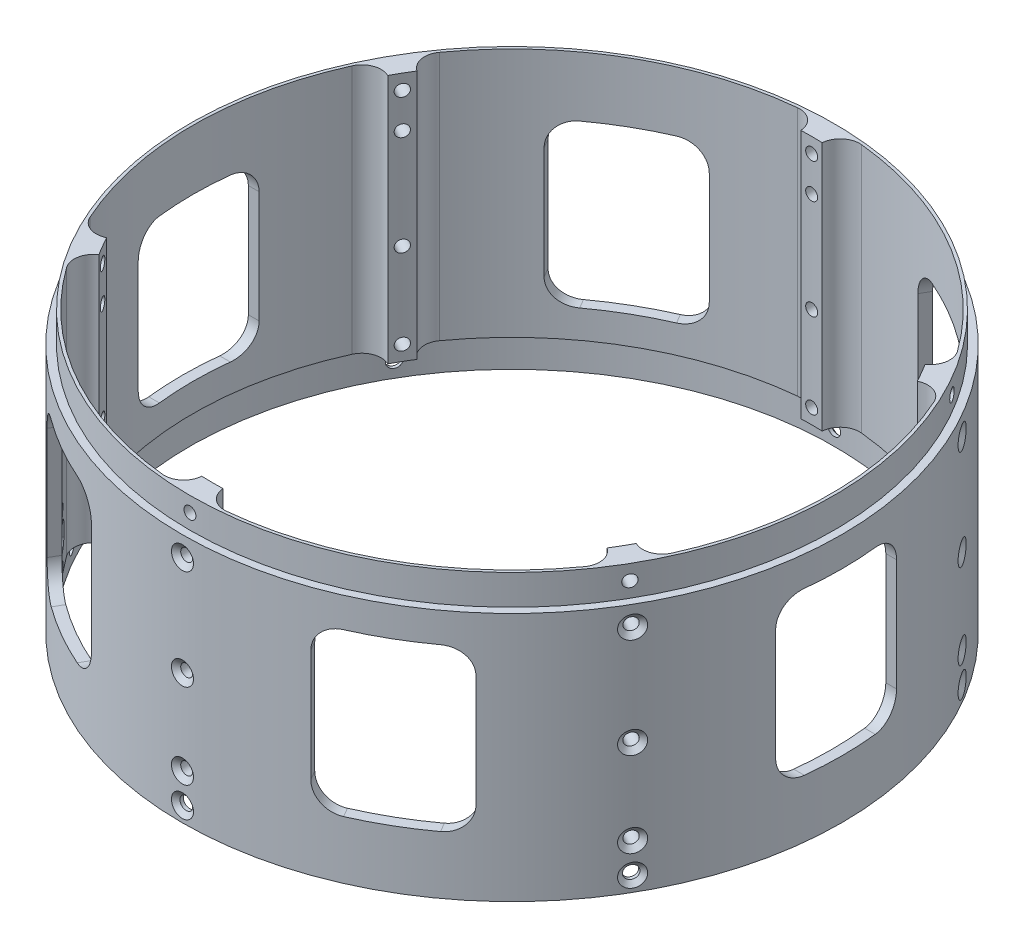
SolidWorks part; units mm, degrees
material "6061-T6 (SS)"
ref_plane "Front Plane" through (0, 0, 0) normal (0, 0, 1) x (1, 0, 0)
ref_plane "Top Plane" through (0, 0, 0) normal (0, 1, 0) x (1, 0, 0)
ref_plane "Right Plane" through (0, 0, 0) normal (1, 0, 0) x (0, 0, -1)
sketch "Sketch1" plane through (0, 0, 0) normal (0, 0, 1) x (1, 0, 0)
  line L0 (0, 42.3951) -> (0, -32.8937) construction
  line L1 (0, -35.6235) -> (0, 35.6235) construction
  line L2 (76.2, -63.5) -> (76.2, 0)
  line L3 (76.2, 0) -> (81.8896, 0)
  line L4 (81.8896, 0) -> (81.8896, -7.6708)
  line L5 (81.8896, -7.6708) -> (83.82, -7.6708)
  line L6 (83.82, -7.6708) -> (83.82, -71.12)
  line L7 (83.82, -71.12) -> (81.9404, -71.12)
  line L8 (81.9404, -71.12) -> (81.9404, -63.5)
  line L9 (81.9404, -63.5) -> (76.2, -63.5)
  line L10 (81.8896, -7.62) -> (84.2911, -7.62) construction
  dimension "D5" = 5.6896
  dimension "D10" = 76.2
  dimension "D2" = 7.62
  dimension "D4" = 7.62
  dimension "D6" = 7.62
revolve "Revolve1" add sketch "Sketch1" angle 360 about L0
sketch "Sketch2" plane through (0, 0, 0) normal (0, 1, 0) x (1, 0, 0)
  line L0 (0, 0) -> (0, 112.6688) construction
  line L1 (0, -35.6235) -> (0, 35.6235) construction
  line L2 (0, 0) -> (-128.6689, 74.287) construction
  line L3 (0, 0) -> (-50.2561, 87.0461) construction
  line L4 (0, 0) -> (-7.6343, 75.8166) construction
  arc A0 (-7.6343, 75.8166) -> (-61.8419, 44.5198) centre (0, 0) ccw construction
  arc A1 (-8.128, 80.7194) -> (-65.841, 47.3988) centre (0, 0) ccw
  arc A2 (-7.1406, 70.9138) -> (-57.8428, 41.6409) centre (0, 0) ccw
  arc A3 (-7.1406, 70.9138) -> (-8.128, 80.7194) centre (-7.6343, 75.8166) ccw
  arc A4 (-65.841, 47.3988) -> (-57.8428, 41.6409) centre (-61.8419, 44.5198) ccw
  circle A5 centre (0, 0) radius 81.8896 construction
  circle A7 centre (0, 0) radius 76.2 construction
  point P5 (-38.1, 65.9911)
  dimension "D2" = 0.762
  dimension "D1" = 60
  dimension "D3" = 30
  dimension "D4" = 5.75
extrude "Cut-Extrude1" cut sketch "Sketch2" against normal through all
pattern_circular "CirPattern1" count 6 over 360 about axis through (0, 42.3951, 0) along (0, 1, 0) of "Cut-Extrude1"
ref_plane "Plane1" through (0, 0, 83.82) normal (0, 0, 1) x (1, 0, 0)
hole_wizard "Tapped Hole for #4-40 Helicoil1" positions "Sketch3" profile "Sketch4" tap size "#4-40" standard "Helicoil® Inch"
sketch "Sketch3" plane through (0, 0, 83.82) normal (0, 0, 1) x (1, 0, 0)
  line L0 (81.8896, 0) -> (-81.8896, 0) construction
  line L1 (2.7181, 0) -> (-2.7181, 0) construction
  line L2 (2.7181, 0) -> (-2.7181, 0) construction
  line L3 (0, 0) -> (0, -3.81) construction
  line L5 (-2.7181, -63.5) -> (2.7181, -63.5) construction
  line L6 (-2.7181, -63.5) -> (2.7181, -63.5) construction
  line L7 (0, -63.5) -> (0, -59.69) construction
  point P0 (0, -3.81)
  point P20 (0, -59.69)
  point P38 (0, -38.1)
  point P40 (0, -12.7)
  dimension "D1" = 3.81
  dimension "D2" = 3.81
  dimension "D3" = 25.4
  dimension "D4" = 50.8
cosmetic thread "Hole Thread1" parameters "D1"=3.556, "D2"=3.7414
sketch "Sketch4" plane through (0, -3.81, 83.82) normal (1, 0, 0) x (0, -1, 0)
  line L0 (0, 0) -> (0, 26.3157)
  line L1 (0, 26.3157) -> (1.524, 25.4)
  line L2 (1.524, 25.4) -> (1.524, 1.1189)
  line L3 (1.524, 1.1189) -> (2.8575, 0)
  line L5 (2.8575, 0) -> (0, 0)
  line L6 (-1.524, 1.1189) -> (-2.8575, 0) construction
  line L10 (0, 26.3157) -> (-1.524, 25.4) construction
  line L11 (0, -6.35) -> (0, 107.95) construction
  dimension "Tap Drill Dia." = 3.048
  dimension "Tap Drill Depth" = 25.4
  dimension "Near C'Sink Dia." = 5.715
  dimension "Near C'Sink Angle" = 100
  dimension "Drill Angle" = 118
cosmetic thread "Hole Thread4" parameters "D1"=3.556, "D2"=3.7414
cosmetic thread "Hole Thread5" parameters "D1"=3.556, "D2"=3.7414
cosmetic thread "Hole Thread6" parameters "D1"=3.556, "D2"=3.7414
hole_wizard "CSK for #4 Flat Head Machine Screw (100)1" positions "Sketch5" profile "Sketch6" countersink size "#4" standard "ANSI Inch"
sketch "Sketch5" plane through (0, 0, 83.82) normal (0, 0, 1) x (1, 0, 0)
  line L0 (-2.7181, -63.5) -> (2.7181, -63.5) construction
  line L1 (-2.7181, -63.5) -> (2.7181, -63.5) construction
  line L2 (0, -63.5) -> (0, -67.31) construction
  point P0 (0, -67.31)
  dimension "D1" = 3.81
sketch "Sketch6" plane through (0, -67.31, 83.82) normal (1, 0, 0) x (0, -1, 0)
  line L0 (0, 0) -> (0, 26.3806)
  line L1 (0, 26.3806) -> (1.6319, 25.4)
  line L2 (1.6319, 25.4) -> (1.6319, 1.0284)
  line L3 (1.6319, 1.0284) -> (2.8575, 0)
  line L5 (2.8575, 0) -> (0, 0)
  line L6 (-1.6319, 1.0284) -> (-2.8575, 0) construction
  line L10 (0, 26.3806) -> (-1.632, 25.4) construction
  line L11 (0, -6.35) -> (0, 107.95) construction
  dimension "Hole Dia." = 3.2639
  dimension "Hole Depth" = 25.4
  dimension "Near C'Sink Dia." = 5.715
  dimension "Near C'Sink Angle" = 100
  dimension "Drill Angle" = 118
pattern_circular "CirPattern2" count 6 over 360 about axis through (0, 42.3951, 0) along (0, 1, 0) of "Tapped Hole for #4-40 Helicoil1", "CSK for #4 Flat Head Machine Screw (100)1"
sketch "Sketch7" plane through (0, 0, 0) normal (1, 0, 0) x (0, 0, -1)
  line L1 (-9.017, -15.24) -> (9.017, -15.24)
  line L2 (-15.367, -21.59) -> (-15.367, -50.038)
  line L3 (-9.017, -56.388) -> (9.017, -56.388)
  line L4 (15.367, -21.59) -> (15.367, -50.038)
  line L5 (-15.367, -15.24) -> (15.367, -56.388) construction
  line L6 (-15.367, -56.388) -> (15.367, -15.24) construction
  arc A0 (-15.367, -50.038) -> (-9.017, -56.388) centre (-9.017, -50.038) ccw
  arc A1 (9.017, -56.388) -> (15.367, -50.038) centre (9.017, -50.038) ccw
  arc A2 (15.367, -21.59) -> (9.017, -15.24) centre (9.017, -21.59) ccw
  arc A3 (-9.017, -15.24) -> (-15.367, -21.59) centre (-9.017, -21.59) ccw
  point P0 (0, -35.814)
  dimension "D4" = 6.35
  dimension "D1" = 41.148
  dimension "D2" = 30.734
  dimension "D3" = 15.24
extrude "Cut-Extrude2" cut sketch "Sketch7" against normal through all and the other way through all
pattern_circular "CirPattern5" count 3 over 360 about axis through (0, -7.6708, 0) along (0, 1, 0) of "Cut-Extrude2"
ref_plane "Plane2" through (0, 0, 0) normal (-0.7071, 0, 0.7071) x (0.7071, 0, 0.7071)
sketch "Sketch8" plane through (0, 0, 0) normal (-0.7071, 0, 0.7071) x (0.7071, 0, 0.7071)
  line L0 (0, 0) -> (89.1919, 0) construction
  line L1 (-9.017, -17.145) -> (-6.858, -17.145)
  line L2 (-12.192, -20.32) -> (-12.192, -31.115)
  line L3 (-9.017, -34.29) -> (-6.858, -34.29)
  line L4 (-3.683, -20.32) -> (-3.683, -31.115)
  line L5 (0, 0) -> (0, -89.2767) construction
  line L6 (-83.82, -71.12) -> (83.82, -71.12) construction
  line L7 (-7.9375, -52.07) -> (-4.7625, -52.07)
  line L8 (-9.525, -53.6575) -> (-9.525, -56.8325)
  line L9 (-7.9375, -58.42) -> (-4.7625, -58.42)
  line L10 (-3.175, -53.6575) -> (-3.175, -56.8325)
  arc A0 (-9.017, -34.29) -> (-12.192, -31.115) centre (-9.017, -31.115) cw
  arc A1 (-3.683, -31.115) -> (-6.858, -34.29) centre (-6.858, -31.115) cw
  arc A2 (-3.683, -20.32) -> (-6.858, -17.145) centre (-6.858, -20.32) ccw
  arc A3 (-9.017, -17.145) -> (-12.192, -20.32) centre (-9.017, -20.32) ccw
  arc A4 (-9.525, -56.8325) -> (-7.9375, -58.42) centre (-7.9375, -56.8325) ccw
  arc A5 (-3.175, -56.8325) -> (-4.7625, -58.42) centre (-4.7625, -56.8325) cw
  arc A6 (-3.175, -53.6575) -> (-4.7625, -52.07) centre (-4.7625, -53.6575) ccw
  arc A7 (-7.9375, -52.07) -> (-9.525, -53.6575) centre (-7.9375, -53.6575) ccw
  circle A8 centre (-6.35, -48.895) radius 1.5875
  circle A9 centre (-6.35, -61.595) radius 1.5875
  point P20 (-3.175, -55.245)
  point P29 (-6.35, -58.42)
  point P36 (0, 0)
  point P37 (-6.0964, -61.9867)
  point P38 (0, 0)
  point P39 (0, 0)
  dimension "D1" = 3.175
  dimension "D8" = 1.5875
  dimension "D11" = 3.175
  dimension "D12" = 3.175
  dimension "D2" = 8.509
  dimension "D3" = 17.145
  dimension "D4" = 17.145
  dimension "D5" = 3.683
  dimension "D6" = 6.35
  dimension "D7" = 6.35
  dimension "D9" = 6.35
  dimension "D10" = 12.7
  dimension "D13" = 3.175
  dimension "D14" = 3.175
extrude "Cut-Extrude3" cut sketch "Sketch8" along normal through all
equation "\"nominalLength\"=2.5"
equation "\"D8@Sketch1\"=\"nominalLength\""
equation "\"D12@Sketch8\"=\"D11@Sketch8\""
